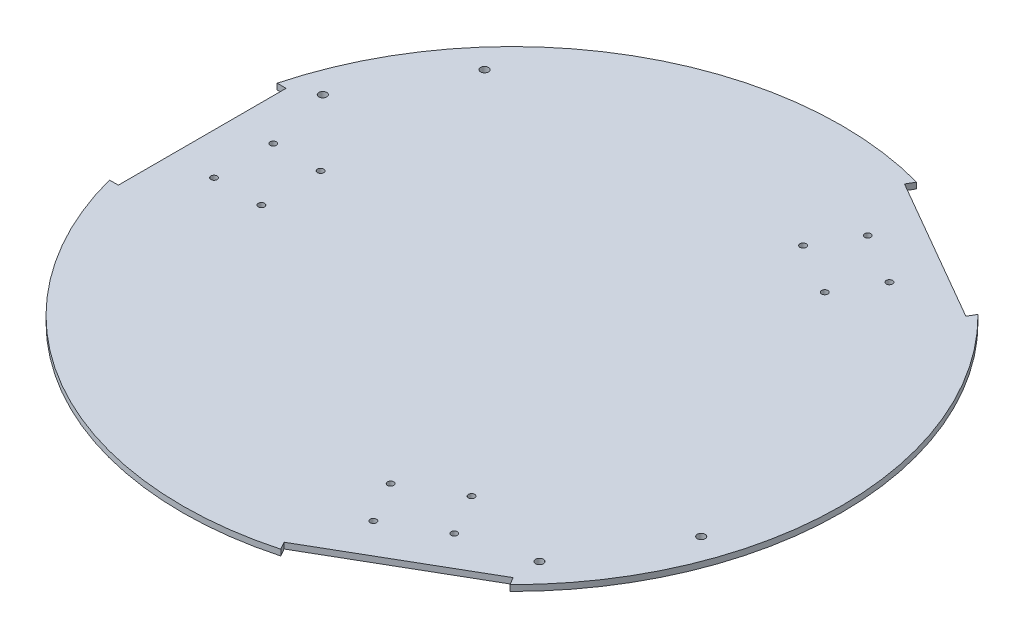
SolidWorks part; units mm, degrees
ref_plane "前视基准面" through (0, 0, 0) normal (0, 0, 1) x (1, 0, 0)
ref_plane "上视基准面" through (0, 0, 0) normal (0, 1, 0) x (1, 0, 0)
ref_plane "右视基准面" through (0, 0, 0) normal (1, 0, 0) x (0, 0, -1)
other "Configuration Table"
sketch "草图2" plane through (0, 0, 0) normal (0, 1, 0) x (1, 0, 0)
  circle A0 centre (0, 0) radius 167
  dimension "D1" = 334
extrude "凸台-拉伸1" add sketch "草图2" along normal blind 3
sketch "草图1" plane through (0, 0, 0) normal (0, 1, 0) x (1, 0, 0)
  line L0 (0, 0) -> (-167, 0) construction
  line L1 (-136, -15) -> (-112, -15) construction
  line L2 (-136, -15) -> (-136, 15) construction
  line L3 (-136, 15) -> (-112, 15) construction
  line L4 (-112, -15) -> (-112, 15) construction
  line L5 (-136, -15) -> (-112, 15) construction
  line L6 (-136, 15) -> (-112, -15) construction
  circle A1 centre (-112, 15) radius 1.6
  circle A2 centre (-112, -15) radius 1.6
  circle A3 centre (-136, 15) radius 1.6
  circle A4 centre (-136, -15) radius 1.6
  point P3 (-124, 0)
  dimension "D5" = 3.2
  dimension "D6" = 3.2
  dimension "D7" = 3.2
  dimension "D8" = 3.2
  dimension "D2" = 112
  dimension "D3" = 24
  dimension "D4" = 30
extrude "切除-拉伸3" cut sketch "草图1" along normal up to next
ref_axis "基准轴1" through (0, 81.4004, 0) along (0, -1, 0)
pattern_circular "阵列(圆周)1" count 3 over 360 about axis through (0, 81.4004, 0) along (0, -1, 0) of "切除-拉伸3"
sketch "草图3" plane through (0, 3, 0) normal (0, 1, 0) x (1, 0, 0)
  line L0 (0, 0) -> (124.4289, 0) construction
  line L1 (-157, -42.5) -> (-247.1247, -42.5)
  line L2 (-157, -42.5) -> (-157, 42.5)
  line L3 (-157, 42.5) -> (-247.1247, 42.5)
  line L4 (-247.1247, -42.5) -> (-247.1247, 42.5)
  line L5 (-157, -42.5) -> (-247.1247, 42.5) construction
  line L6 (-157, 42.5) -> (-247.1247, -42.5) construction
  point P0 (-202.0623, 0)
  dimension "D1" = 157
  dimension "D2" = 85
extrude "切除-拉伸4" cut sketch "草图3" against normal up to next
pattern_circular "阵列(圆周)2" count 3 over 360 about axis through (0, 81.4004, 0) along (0, -1, 0) of "切除-拉伸4"
ref_plane "基准面1" through (0, 0, 0) normal (-0.866, 0, -0.5) x (-0.5, 0, 0.866)
ref_plane "基准面2" through (0, 0, 0) normal (0.5, 0, -0.866) x (-0.866, 0, -0.5)
sketch "草图4" plane through (0, 0, 0) normal (0, -1, 0) x (1, 0, 0)
  line L0 (-1.4289, -0.825) -> (1.4289, 0.825) construction
  line L1 (-0.825, 1.4289) -> (0.825, -1.4289) construction
  circle A0 centre (-144.9038, -49.0192) radius 2
  point P6 (-21.5694, 18.2808)
  point P7 (0, 0)
  point P8 (-20.4382, 22.3016)
  dimension "D1" = 4
  dimension "D2" = 30
  dimension "D3" = 150
extrude "切除-拉伸5" cut sketch "草图4" against normal blind 10
mirror "镜向1" about plane through (0, 0, 0) normal (0.5, 0, -0.866) of "切除-拉伸5"
mirror "镜向2" about plane through (0, 0, 0) normal (-0.866, 0, -0.5) of "切除-拉伸5", "镜向1"
